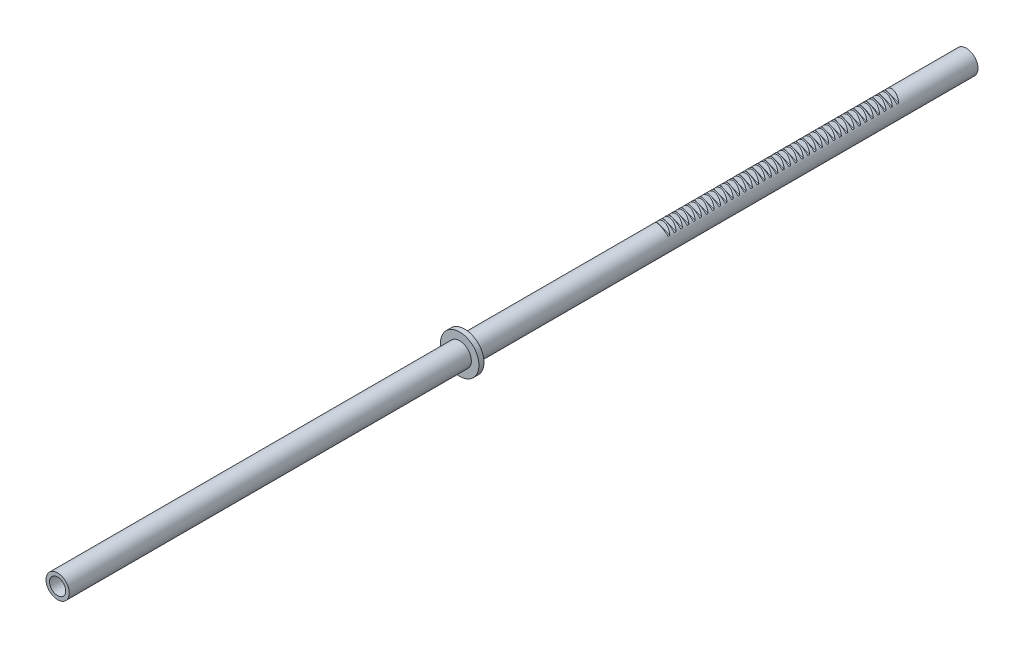
SolidWorks part; units mm, degrees
material "1.0718 (11SMnPb30)"
ref_plane "Front Plane" through (0, 0, 0) normal (0, 0, 1) x (1, 0, 0)
ref_plane "Top Plane" through (0, 0, 0) normal (0, 1, 0) x (1, 0, 0)
ref_plane "Right Plane" through (0, 0, 0) normal (1, 0, 0) x (0, 0, -1)
sketch "Sketch5" plane through (0, 0, 0) normal (0, 0, 1) x (1, 0, 0)
  circle A0 centre (0, 0) radius 11.5
extrude "Boss-Extrude13" add sketch "Sketch5" along normal blind 598
ref_plane "Plane2" through (11.5, 0, 0) normal (1, 0, 0) x (0, 0, -1)
sketch "Sketch6" plane through (11.5, 0, 0) normal (1, 0, 0) x (0, 0, -1)
  line L0 (0, -11.5) -> (0, 11.5) construction
  line L1 (0, 11.5) -> (-598, 11.5) construction
  line L2 (-78.3621, 7) -> (-80, 11.5)
  line L3 (-80, 11.5) -> (-81.2837, 11.5)
  line L4 (-81.2837, 11.5) -> (-82.9216, 7)
  line L5 (-82.9216, 7) -> (-84.6453, 7)
  line L6 (-84.6453, 7) -> (-86.2832, 11.5)
  line L7 (-86.2832, 11.5) -> (-87.5669, 11.5)
  line L8 (-87.5669, 11.5) -> (-89.2048, 7)
  line L9 (-89.2048, 7) -> (-90.9285, 7)
  line L10 (-90.9285, 7) -> (-92.5664, 11.5)
  line L11 (-92.5664, 11.5) -> (-93.8501, 11.5)
  line L12 (-93.8501, 11.5) -> (-95.4879, 7)
  line L13 (-95.4879, 7) -> (-97.2117, 7)
  line L14 (-97.2117, 7) -> (-98.8496, 11.5)
  line L15 (-98.8496, 11.5) -> (-100.1333, 11.5)
  line L16 (-100.1333, 11.5) -> (-101.7711, 7)
  line L17 (-101.7711, 7) -> (-103.4949, 7)
  line L18 (-103.4949, 7) -> (-105.1327, 11.5)
  line L19 (-105.1327, 11.5) -> (-106.4165, 11.5)
  line L20 (-106.4165, 11.5) -> (-108.0543, 7)
  line L21 (-108.0543, 7) -> (-109.7781, 7)
  line L22 (-109.7781, 7) -> (-111.4159, 11.5)
  line L23 (-111.4159, 11.5) -> (-112.6996, 11.5)
  line L24 (-112.6996, 11.5) -> (-114.3375, 7)
  line L25 (-114.3375, 7) -> (-116.0612, 7)
  line L26 (-116.0612, 7) -> (-117.6991, 11.5)
  line L27 (-117.6991, 11.5) -> (-118.9828, 11.5)
  line L28 (-118.9828, 11.5) -> (-120.6207, 7)
  line L29 (-120.6207, 7) -> (-122.3444, 7)
  line L30 (-122.3444, 7) -> (-123.9823, 11.5)
  line L31 (-123.9823, 11.5) -> (-125.266, 11.5)
  line L32 (-125.266, 11.5) -> (-126.9039, 7)
  line L33 (-126.9039, 7) -> (-128.6276, 7)
  line L34 (-128.6276, 7) -> (-130.2655, 11.5)
  line L35 (-130.2655, 11.5) -> (-131.5492, 11.5)
  line L36 (-131.5492, 11.5) -> (-133.1871, 7)
  line L37 (-133.1871, 7) -> (-134.9108, 7)
  line L38 (-134.9108, 7) -> (-136.5487, 11.5)
  line L39 (-136.5487, 11.5) -> (-137.8324, 11.5)
  line L40 (-137.8324, 11.5) -> (-139.4702, 7)
  line L41 (-139.4702, 7) -> (-141.194, 7)
  line L42 (-141.194, 7) -> (-142.8319, 11.5)
  line L43 (-142.8319, 11.5) -> (-144.1156, 11.5)
  line L44 (-144.1156, 11.5) -> (-145.7534, 7)
  line L45 (-145.7534, 7) -> (-147.4772, 7)
  line L46 (-147.4772, 7) -> (-149.115, 11.5)
  line L47 (-149.115, 11.5) -> (-150.3988, 11.5)
  line L48 (-150.3988, 11.5) -> (-152.0366, 7)
  line L49 (-152.0366, 7) -> (-153.7604, 7)
  line L50 (-153.7604, 7) -> (-155.3982, 11.5)
  line L51 (-155.3982, 11.5) -> (-156.6819, 11.5)
  line L52 (-156.6819, 11.5) -> (-158.3198, 7)
  line L53 (-158.3198, 7) -> (-160.0435, 7)
  line L54 (-160.0435, 7) -> (-161.6814, 11.5)
  line L55 (-161.6814, 11.5) -> (-162.9651, 11.5)
  line L56 (-162.9651, 11.5) -> (-164.603, 7)
  line L57 (-164.603, 7) -> (-166.3267, 7)
  line L58 (-166.3267, 7) -> (-167.9646, 11.5)
  line L59 (-167.9646, 11.5) -> (-169.2483, 11.5)
  line L60 (-169.2483, 11.5) -> (-170.8862, 7)
  line L61 (-170.8862, 7) -> (-172.6099, 7)
  line L62 (-172.6099, 7) -> (-174.2478, 11.5)
  line L63 (-174.2478, 11.5) -> (-175.5315, 11.5)
  line L64 (-175.5315, 11.5) -> (-177.1694, 7)
  line L65 (-177.1694, 7) -> (-178.8931, 7)
  line L66 (-178.8931, 7) -> (-180.531, 11.5)
  line L67 (-180.531, 11.5) -> (-181.8147, 11.5)
  line L68 (-181.8147, 11.5) -> (-183.4525, 7)
  line L69 (-183.4525, 7) -> (-185.1763, 7)
  line L70 (-185.1763, 7) -> (-186.8142, 11.5)
  line L71 (-186.8142, 11.5) -> (-188.0979, 11.5)
  line L72 (-188.0979, 11.5) -> (-189.7357, 7)
  line L73 (-189.7357, 7) -> (-191.4595, 7)
  line L74 (-191.4595, 7) -> (-193.0973, 11.5)
  line L75 (-193.0973, 11.5) -> (-194.381, 11.5)
  line L76 (-194.381, 11.5) -> (-196.0189, 7)
  line L77 (-196.0189, 7) -> (-197.7427, 7)
  line L78 (-197.7427, 7) -> (-199.3805, 11.5)
  line L79 (-199.3805, 11.5) -> (-200.6642, 11.5)
  line L80 (-200.6642, 11.5) -> (-202.3021, 7)
  line L81 (-78.3621, 7) -> (-76.6421, 7)
  line L82 (-76.6421, 7) -> (-74.4318, 13.0727)
  line L83 (-202.3021, 7) -> (-204.0221, 7)
  line L84 (-204.0221, 7) -> (-206.2324, 13.0727)
  line L85 (-206.2324, 13.0727) -> (-74.4318, 13.0727)
  dimension "D1" = 110
  dimension "D2" = 80
sketch "Sketch7" plane through (0, 0, 0) normal (0, 1, 0) x (1, 0, 0)
  line L0 (25.1541, -50.7969) -> (-17.1418, -39.0434)
  line L1 (11.5, 0) -> (-11.5, 0) construction
  dimension "D1" = 15.53
sweep "Swept-Cut1" cut profiles "Sketch6" path "Sketch7"
sketch "Sketch8" plane through (0, 0, 0) normal (0, 1, 0) x (1, 0, 0)
  line L0 (0, 0) -> (0, -598) construction
  line L1 (-11.5, -598) -> (11.5, -598) construction
sketch "Sketch11" plane through (0, 0, 0) normal (1, 0, 0) x (0, 0, -1)
  line L0 (-380, 19) -> (-380, 11.5)
  line L1 (-382.5, 19) -> (-380, 19)
  line L2 (-388.1613, 22.9259) -> (-382.5, 19)
  line L3 (-388.2738, 17.9272) -> (-388.1613, 22.9259)
  line L4 (-387.6539, 15.5053) -> (-388.2738, 17.9272)
  line L5 (-390, 14.6417) -> (-387.6539, 15.5053)
  line L6 (-390, 14.6417) -> (-390, 11.5)
  line L7 (-390, 11.5) -> (-380, 11.5)
  line L8 (-598, 11.5) -> (-598, -11.5) construction
  dimension "D1" = 208
  dimension "D2" = 2.5
  dimension "D3" = 2.5
  dimension "D4" = 5
  dimension "D5" = 7.5
  dimension "D6" = 2.5
revolve "Revolve1" add sketch "Sketch11" angle 360 about L0 other way angle 360
sketch "Sketch1" plane through (0, 0, 598) normal (0, 0, 1) x (1, 0, 0)
  circle A0 centre (0, 0) radius 8
  dimension "D1" = 16
extrude "Cut-Extrude2" cut sketch "Sketch1" against normal blind 17
sketch "Sketch4" plane through (0, 0, 598) normal (0, 0, 1) x (1, 0, 0)
  circle A0 centre (0, 0) radius 8
sketch "Sketch9" plane through (0, 0, 0) normal (0, 0, -1) x (-1, 0, 0)
  circle A0 centre (0, 0) radius 8
  dimension "D1" = 16
extrude "Cut-Extrude3" cut sketch "Sketch9" against normal blind 25
sketch "Sketch14" plane through (11.5, 0, 0) normal (1, 0, 0) x (0, 0, -1)
  line L0 (-208.5778, 7) -> (-206.3688, 13.0693)
  line L1 (-255.9152, 11.5) -> (-254.2801, 7)
  line L2 (-255.9152, 11.5) -> (-257.1952, 11.5)
  line L4 (-304.5326, 7) -> (-306.7416, 13.0693)
  line L5 (-304.5326, 7) -> (-302.8126, 7)
  line L6 (-302.8126, 7) -> (-301.1747, 11.5)
  line L7 (-301.1747, 11.5) -> (-299.891, 11.5)
  line L8 (-299.891, 11.5) -> (-298.2532, 7)
  line L9 (-298.2532, 7) -> (-296.5294, 7)
  line L10 (-296.5294, 7) -> (-294.8916, 11.5)
  line L11 (-294.8916, 11.5) -> (-293.6078, 11.5)
  line L12 (-293.6078, 11.5) -> (-291.97, 7)
  line L13 (-291.97, 7) -> (-290.2462, 7)
  line L14 (-290.2462, 7) -> (-288.6084, 11.5)
  line L15 (-288.6084, 11.5) -> (-287.3247, 11.5)
  line L16 (-287.3247, 11.5) -> (-285.6868, 7)
  line L17 (-285.6868, 7) -> (-283.9631, 7)
  line L18 (-283.9631, 7) -> (-282.3252, 11.5)
  line L19 (-282.3252, 11.5) -> (-281.0415, 11.5)
  line L20 (-281.0415, 11.5) -> (-279.4036, 7)
  line L21 (-279.4036, 7) -> (-277.6799, 7)
  line L22 (-277.6799, 7) -> (-276.042, 11.5)
  line L23 (-276.042, 11.5) -> (-274.7583, 11.5)
  line L24 (-274.7583, 11.5) -> (-273.1204, 7)
  line L25 (-273.1204, 7) -> (-271.3967, 7)
  line L26 (-271.3967, 7) -> (-269.7588, 11.5)
  line L27 (-269.7588, 11.5) -> (-268.4751, 11.5)
  line L28 (-268.4751, 11.5) -> (-266.8372, 7)
  line L29 (-266.8372, 7) -> (-265.1135, 7)
  line L30 (-265.1135, 7) -> (-263.4756, 11.5)
  line L31 (-263.4756, 11.5) -> (-262.1919, 11.5)
  line L32 (-262.1919, 11.5) -> (-260.5541, 7)
  line L33 (-260.5541, 7) -> (-258.8303, 7)
  line L34 (-252.5564, 7) -> (-254.2801, 7)
  line L35 (-250.9185, 11.5) -> (-252.5564, 7)
  line L36 (-249.6348, 11.5) -> (-250.9185, 11.5)
  line L37 (-247.9969, 7) -> (-249.6348, 11.5)
  line L38 (-246.2732, 7) -> (-247.9969, 7)
  line L39 (-244.6353, 11.5) -> (-246.2732, 7)
  line L40 (-243.3516, 11.5) -> (-244.6353, 11.5)
  line L41 (-241.7138, 7) -> (-243.3516, 11.5)
  line L42 (-239.99, 7) -> (-241.7138, 7)
  line L43 (-238.3521, 11.5) -> (-239.99, 7)
  line L44 (-237.0684, 11.5) -> (-238.3521, 11.5)
  line L45 (-235.4306, 7) -> (-237.0684, 11.5)
  line L46 (-233.7068, 7) -> (-235.4306, 7)
  line L47 (-232.069, 11.5) -> (-233.7068, 7)
  line L48 (-230.7853, 11.5) -> (-232.069, 11.5)
  line L49 (-229.1474, 7) -> (-230.7853, 11.5)
  line L50 (-227.4236, 7) -> (-229.1474, 7)
  line L51 (-225.7858, 11.5) -> (-227.4236, 7)
  line L52 (-224.5021, 11.5) -> (-225.7858, 11.5)
  line L53 (-222.8642, 7) -> (-224.5021, 11.5)
  line L54 (-221.1405, 7) -> (-222.8642, 7)
  line L55 (-219.5026, 11.5) -> (-221.1405, 7)
  line L56 (-218.2189, 11.5) -> (-219.5026, 11.5)
  line L57 (-216.581, 7) -> (-218.2189, 11.5)
  line L58 (-214.8573, 7) -> (-216.581, 7)
  line L59 (-213.2194, 11.5) -> (-214.8573, 7)
  line L60 (-211.9357, 11.5) -> (-213.2194, 11.5)
  line L61 (-210.2978, 7) -> (-211.9357, 11.5)
  line L62 (-208.5778, 7) -> (-210.2978, 7)
  line L63 (-257.1952, 11.5) -> (-258.8303, 7)
  line L64 (-306.7416, 13.0693) -> (-256.4854, 13.0693)
  line L69 (-256.4854, 13.0693) -> (-206.3688, 13.0693)
sweep "Cut-Sweep1" cut profiles "Sketch14" path "Çizim7<3>"
sketch "Çizim7<3>" plane through (0, 0, 0) normal (0, 1, 0) x (1, 0, 0) same geometry as "Sketch7"
sketch "Sketch22" plane through (0, 0, 380) normal (0, 0, -1) x (-1, 0, 0)
  circle A0 centre (0, 0) radius 19
  circle A1 centre (0, 0) radius 29.0201
extrude "Cut-Extrude4" cut sketch "Sketch22" against normal blind 10
sketch "Sketch23" plane through (0, 0, 598) normal (0, 0, 1) x (1, 0, 0)
  circle A0 centre (0, 0) radius 8
extrude "Boss-Extrude1" add sketch "Sketch23" against normal blind 17
sketch "Sketch24" plane through (0, 0, 598) normal (0, 0, 1) x (1, 0, 0)
  circle A0 centre (0, 0) radius 11.5
extrude "Boss-Extrude2" add sketch "Sketch24" along normal blind 300
sketch "Sketch25" plane through (0, 0, 898) normal (0, 0, 1) x (1, 0, 0)
  circle A0 centre (0, 0) radius 8
  dimension "D1" = 16
extrude "Cut-Extrude5" cut sketch "Sketch25" against normal blind 25
sketch "Sketch26" plane through (0, 0, 380) normal (0, 0, -1) x (-1, 0, 0)
  line L0 (0, 19) -> (0.2438, 18.8259)
  line L1 (1.4928, 17.9342) -> (15.8052, 7.7162)
  circle A0 centre (0, 0) radius 18.8275
  arc A1 (1.4928, 17.9342) -> (15.8052, 7.7162) centre (-0.5073, 0) ccw
  circle A2 centre (0, 0) radius 19 construction
extrude "Boss-Extrude3" add sketch "Sketch26" along normal blind 14.86 contours A0 A1 L1 region at (13.3611, -13.1892, 380)
ref_plane "Plane1" through (0, 0, 631.57) normal (0, 0, -1) x (-1, 0, 0)
sketch "Sketch27" plane through (0, 0, 631.57) normal (0, 0, -1) x (-1, 0, 0)
  circle A0 centre (0, 0) radius 19
  dimension "D1" = 38
sketch "Sketch29" plane through (0, 0, 380) normal (0, 0, -1) x (-1, 0, 0)
  circle A0 centre (0, 0) radius 21.7773
  circle A1 centre (0, 0) radius 11.5
extrude "Cut-Extrude7" cut sketch "Sketch29" along normal blind 36
sketch "Sketch30" plane through (0, 0, 380) normal (0, 0, -1) x (-1, 0, 0)
  circle A0 centre (0, 0) radius 11.5
  circle A1 centre (0, 0) radius 19
extrude "Cut-Extrude8" cut sketch "Sketch30" against normal blind 18
extrude "Boss-Extrude9" add sketch "Sketch27" against normal blind 10.03
sketch "Sketch33" plane through (0, 0, 641.6) normal (0, 0, 1) x (1, 0, 0)
  line L1 (0.8217, 15.2786) -> (-11.2945, 15.2786)
  line L2 (-11.2945, 15.2786) -> (12.9379, 15.2786)
  circle A0 centre (0, 0) radius 19 construction
  arc A1 (12.9379, 15.2786) -> (-11.2945, 15.2786) centre (0.8217, 15.2786) ccw
  circle M2 centre (0, 0) radius 19
extrude "Cut-Extrude9" cut sketch "Sketch33" against normal blind 10.03 contours L1 L2 M2 | L2 A1 M2 region at (0, 16.7804, 641.6) region at (1.0931, 21.6229, 641.6)
sketch "Sketch35" plane through (0, 0, 641.6) normal (0, 0, 1) x (1, 0, 0)
  line L1 (-11.2945, 15.2786) -> (12.6595, 15.2786)
  line L2 (-11.2945, 15.2786) -> (-11.2945, 18.2437)
  line L3 (-11.2945, 18.2437) -> (12.6595, 18.2437)
  line L4 (12.6595, 15.2786) -> (12.6595, 18.2437)
extrude "Boss-Extrude10" add sketch "Sketch35" against normal blind 147.5
sketch "Sketch36" plane through (12.6595, 0, 0) normal (1, 0, 0) x (0, 0, -1)
  line L1 (-494.1, 15.2786) -> (-500.68, 15.2786)
  line L2 (-494.1, 15.2786) -> (-494.1, 20.409)
  line L3 (-494.1, 20.409) -> (-500.68, 20.409)
  line L4 (-500.68, 15.2786) -> (-500.68, 20.409)
  dimension "D1" = 6.58
extrude "Cut-Extrude10" cut sketch "Sketch36" against normal blind 147.5
sketch "Sketch37" plane through (0, 0, 500.68) normal (0, 0, -1) x (-1, 0, 0)
  circle A0 centre (0, 0) radius 19
  dimension "D1" = 38
extrude "Boss-Extrude11" add sketch "Sketch37" along normal blind 5
sketch "Sketch38" plane through (0, 0, 500.68) normal (0, 0, -1) x (-1, 0, 0)
  line L1 (-12.6595, 18.2437) -> (11.2945, 18.2437)
  line L2 (-12.6595, 18.2437) -> (-12.6595, 15.2786)
  line L3 (-12.6595, 15.2786) -> (11.2945, 15.2786)
  line L4 (11.2945, 18.2437) -> (11.2945, 15.2786)
extrude "Cut-Extrude11" cut sketch "Sketch38" against normal blind 182
sketch "Sketch39" plane through (0, 0, 631.57) normal (0, 0, -1) x (-1, 0, 0)
  circle A0 centre (0, 0) radius 11.5
  circle A1 centre (0, 0) radius 19
extrude "Cut-Extrude12" cut sketch "Sketch39" against normal blind 34
